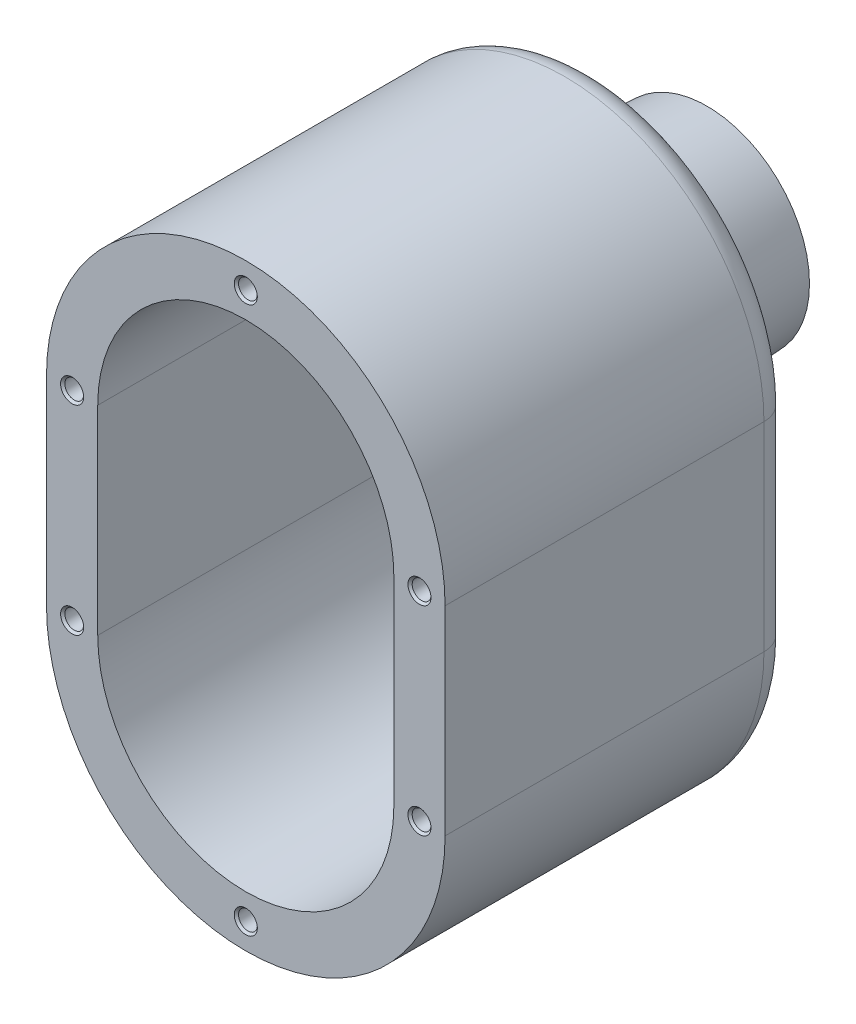
SolidWorks part; units mm, degrees
ref_plane "Front Plane" through (0, 0, 0) normal (0, 0, 1) x (1, 0, 0)
ref_plane "Top Plane" through (0, 0, 0) normal (0, 1, 0) x (1, 0, 0)
ref_plane "Right Plane" through (0, 0, 0) normal (1, 0, 0) x (0, 0, -1)
sketch "Sketch2" plane through (0, 0, 0) normal (0, 0, 1) x (1, 0, 0)
  line L0 (0, -17.5) -> (0, 17.5) construction
  line L1 (-35, -17.5) -> (-35, 17.5)
  line L2 (35, -17.5) -> (35, 17.5)
  arc A0 (-35, -17.5) -> (35, -17.5) centre (0, -17.5) ccw
  arc A1 (35, 17.5) -> (-35, 17.5) centre (0, 17.5) ccw
  point P2 (0, 0)
  dimension "D1" = 35
  dimension "D2" = 35
extrude "Boss-Extrude3" add sketch "Sketch2" along normal mid plane 58
shell "Shell9" thickness 9 removed face at (0, 0, 29)
sketch "Sketch3" plane through (0, 0, 0) normal (1, 0, 0) x (0, 0, -1)
  line L0 (29, 17.5) -> (49, 17.5)
  line L2 (29, -17.5) -> (29, 17.5) construction
  line L4 (49, -0.5) -> (49, 17.5)
  line L5 (29, -1.7644) -> (49, -0.5)
  line L6 (29, 17.5) -> (29, -1.7644)
  dimension "D1" = 18
  dimension "D2" = 20
revolve "Revolve1" add sketch "Sketch3" angle 360 about L0
sketch "Sketch4" plane through (0, 0, 0) normal (1, 0, 0) x (0, 0, -1)
  line L0 (20, 17.5) -> (20, 36.5489)
  line L1 (-29, 17.5) -> (29, 17.5) construction
  line L2 (20, 36.5489) -> (5, 35.5)
  line L3 (5, 35.5) -> (5, 17.5)
  line L4 (5, 17.5) -> (20, 17.5)
  line L5 (29, -1.7644) -> (29, 36.7644) construction
  line L6 (5, 35.5) -> (69.0806, 35.5) construction
  dimension "D1" = 9
  dimension "D2" = 18
  dimension "D3" = 15
  dimension "D4" = 4
revolve "Revolve2" add sketch "Sketch4" angle 360 about L4
sketch "Sketch5" plane through (0, 0, 0) normal (1, 0, 0) x (0, 0, -1)
  line L0 (20, -17.5) -> (20, -6.95)
  line L1 (-29, -17.5) -> (29, -17.5) construction
  line L2 (20, -6.95) -> (5, -8)
  line L3 (5, -8) -> (5, -17.5)
  line L4 (5, -17.5) -> (20, -17.5)
  line L5 (5, -8) -> (69.1367, -8) construction
  line L6 (29, -17.5) -> (29, 17.5) construction
  dimension "D1" = 9.5
  dimension "D2" = 15
  dimension "D3" = 10.55
  dimension "D4" = 9
revolve "Revolve4" add sketch "Sketch5" angle 360 about L4
sketch "Sketch6" plane through (0, 0, -49) normal (0, 0, -1) x (-1, 0, 0)
  circle A0 centre (0, 17.5) radius 14
  dimension "D1" = 28
extrude "Cut-Extrude1" cut sketch "Sketch6" against normal blind 15
sketch "Sketch7" plane through (0, 0, -34) normal (0, 0, -1) x (-1, 0, 0)
  circle A0 centre (0, 17.5) radius 10.5
  dimension "D1" = 21
extrude "Cut-Extrude2" cut sketch "Sketch7" against normal blind 6
sketch "Sketch8" plane through (0, 0, -28) normal (0, 0, -1) x (-1, 0, 0)
  circle A0 centre (0, 17.5) radius 9
  dimension "D1" = 18
extrude "Boss-Extrude4" add sketch "Sketch8" against normal blind 14.8
sketch "Sketch9" plane through (0, 0, -28) normal (0, 0, -1) x (-1, 0, 0)
  circle A0 centre (0, 17.5) radius 10.5
  dimension "D1" = 21
extrude "Cut-Extrude3" cut sketch "Sketch9" against normal blind 5
sketch "Sketch10" plane through (0, 0, -23) normal (0, 0, -1) x (-1, 0, 0)
  circle A0 centre (0, 17.5) radius 11
  dimension "D1" = 22
extrude "Cut-Extrude4" cut sketch "Sketch10" against normal blind 1.1
sketch "Sketch11" plane through (0, 0, -5) normal (0, 0, 1) x (1, 0, 0)
  circle A0 centre (0, 17.5) radius 10.5
  dimension "D1" = 21
extrude "Cut-Extrude5" cut sketch "Sketch11" against normal through all
sketch "Sketch12" plane through (0, 0, -5) normal (0, 0, 1) x (1, 0, 0)
  circle A0 centre (0, -17.5) radius 6
  dimension "D1" = 12
extrude "Cut-Extrude6" cut sketch "Sketch12" against normal through all both and the other way through all
sketch "Sketch15" plane through (0, 0, 29) normal (0, 0, 1) x (1, 0, 0)
  line L0 (26, -17.5) -> (26, 17.5) construction
  line L1 (-26, 17.5) -> (-26, -17.5) construction
  line L2 (35, -17.5) -> (35, 17.5)
  line L3 (-35, 17.5) -> (-35, -17.5)
  line L4 (35, -17.5) -> (35, 17.5)
  line L5 (-35, 17.5) -> (-35, -17.5)
  line L6 (26, -17.5) -> (26, 17.5)
  line L7 (-26, 17.5) -> (-26, -17.5)
  arc A0 (-26, -17.5) -> (26, -17.5) centre (0, -17.5) ccw construction
  arc A1 (26, 17.5) -> (-26, 17.5) centre (0, 17.5) ccw construction
  arc A2 (-35, -17.5) -> (35, -17.5) centre (0, -17.5) ccw
  arc A3 (35, 17.5) -> (-35, 17.5) centre (0, 17.5) ccw
  arc A4 (-35, -17.5) -> (35, -17.5) centre (0, -17.5) ccw
  arc A5 (35, 17.5) -> (-35, 17.5) centre (0, 17.5) ccw
  arc A6 (-26, -17.5) -> (26, -17.5) centre (0, -17.5) ccw
  arc A7 (26, 17.5) -> (-26, 17.5) centre (0, 17.5) ccw
  dimension "D1" = 0
extrude "Boss-Extrude6" add sketch "Sketch15" along normal blind 3
sketch "Sketch23" plane through (0, 0, -29) normal (0, 0, -1) x (-1, 0, 0)
  circle A0 centre (0, -17.5) radius 7.5
  circle A1 centre (0, -17.5) radius 6 construction
  circle A2 centre (0, -17.5) radius 6
  dimension "D1" = 15
extrude "Boss-Extrude9" add sketch "Sketch23" along normal blind 2
fillet "Fillet2" radius 5 4 edges at (35, 0, -29) (-35, 0, -29) (0, 52.5, -29) (0, -52.5, -29)
sketch "Sketch27" plane through (0, 0, 32) normal (0, 0, 1) x (1, 0, 0)
  line L0 (0, 43.5) -> (0, 52.5)
  line L1 (-26, 17.5) -> (-35, 17.5)
  line L4 (26, 17.5) -> (35, 17.5)
  line L7 (0, -43.5) -> (0, -52.5)
  line L8 (-35, -17.5) -> (-26, -17.5)
  line L9 (26, -17.5) -> (35, -17.5)
  arc A0 (26, 17.5) -> (-26, 17.5) centre (0, 17.5) ccw construction
  arc A1 (35, 17.5) -> (-35, 17.5) centre (0, 17.5) ccw construction
  arc A2 (-26, -17.5) -> (26, -17.5) centre (0, -17.5) ccw construction
  arc A3 (-35, -17.5) -> (35, -17.5) centre (0, -17.5) ccw construction
  point P16 (0, 48)
  point P17 (-30.5, 17.5)
  point P18 (-30.5, -17.5)
  point P19 (0, -48)
  point P28 (30.5, -17.5)
  point P37 (30.5, 17.5)
hole_wizard "M4 Tapped Hole1" positions "3DSketch1" profile "Sketch29" tap size "M4" standard "ISO"
sketch3d "3DSketch1"
  point P0 (0, 48, 32)
  point P3 (30.5, 17.5, 32)
  point P6 (30.5, -17.5, 32)
  point P9 (0, -48, 32)
  point P12 (-30.5, -17.5, 32)
  point P15 (-30.5, 17.5, 32)
sketch "Sketch29" plane through (0, 48, 32) normal (1, 0, 0) x (0, -1, 0)
  line L0 (0, 0) -> (0, 13.9914)
  line L1 (0, 13.9914) -> (1.65, 13)
  line L2 (1.65, 13) -> (1.65, 0.375)
  line L3 (1.65, 0.375) -> (2.025, 0)
  line L5 (2.025, 0) -> (0, 0)
  line L6 (-1.65, 0.375) -> (-2.025, 0) construction
  line L10 (0, 13.9914) -> (-1.65, 13) construction
  line L11 (0, -6.35) -> (0, 107.95) construction
  dimension "Tap Drill Dia." = 3.3
  dimension "Tap Drill Depth" = 13
  dimension "Near C'Sink Dia." = 4.05
  dimension "Near C'Sink Angle" = 90
  dimension "Drill Angle" = 118
cosmetic thread "Hole Thread1" parameters "D1"=10, "D2"=4
cosmetic thread "Hole Thread2" parameters "D1"=10, "D2"=4
cosmetic thread "Hole Thread3" parameters "D1"=10, "D2"=4
cosmetic thread "Hole Thread4" parameters "D1"=10, "D2"=4
cosmetic thread "Hole Thread5" parameters "D1"=10, "D2"=4
cosmetic thread "Hole Thread6" parameters "D1"=10, "D2"=4
scale "Scale1" scale about centroid uniform scaling yes scale factor 0.317565
